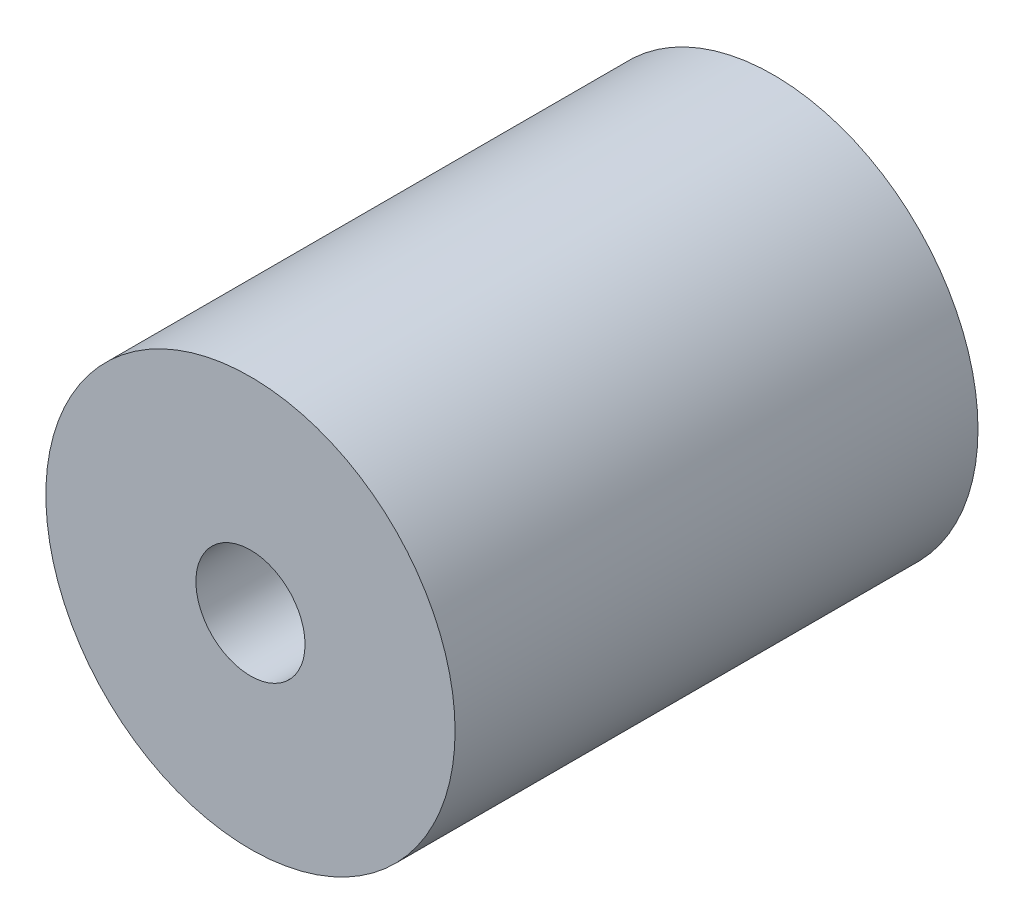
SolidWorks part; units mm, degrees
ref_plane "前视基准面" through (0, 0, 0) normal (0, 0, 1) x (1, 0, 0)
ref_plane "上视基准面" through (0, 0, 0) normal (0, 1, 0) x (1, 0, 0)
ref_plane "右视基准面" through (0, 0, 0) normal (1, 0, 0) x (0, 0, -1)
other "Configuration Table"
sketch "草图1" plane through (0, 0, 0) normal (0, 0, 1) x (1, 0, 0)
  line L0 (0, 0) -> (1.7387, 0.4659) construction
  line L1 (0, 0) -> (1.6291, 0.4551)
  line L2 (0, 0) -> (1.6291, -0.4551)
  line L3 (0, 0) -> (1.7387, -0.4659) construction
  line L4 (0, 0) -> (2.425, 0) construction
  line L5 (1.7387, 0.4659) -> (1.7387, -0.4659) construction
  circle A0 centre (0, 0) radius 1.525
  circle A1 centre (0, 0) radius 2.425
  circle A2 centre (0, 0) radius 1.6914 construction
  circle A3 centre (0, 0) radius 1.8 construction
  circle A4 centre (0, 0) radius 4.5
  spline S0 degree 4 poles (1.6291, 0.4551) (1.6415, 0.4586) (1.6769, 0.4656) (1.746, 0.4684) (1.8576, 0.4574) (1.9985, 0.4209) (2.171, 0.3489) (2.3582, 0.2351) (2.5438, 0.0819) (2.7191, -0.1093) (2.8693, -0.3205) (2.9946, -0.5472) (3.1006, -0.7975) (3.1986, -1.1195) (3.2658, -1.5159) (3.2754, -1.9832) (3.2064, -2.4974) (3.0631, -2.9965) (2.8558, -3.471) (2.5865, -3.9159) (2.2706, -4.3232) (1.901, -4.6937) (1.507, -5.0164) (1.0559, -5.3028) (0.6986, -5.4883) (0.2793, -5.6591) (0.0342, -5.7399) (-0.2484, -5.8241) (-0.3932, -5.8525) (-0.5197, -5.8826) (-0.5587, -5.8884) (-0.5863, -5.894) (-0.6011, -5.8971) knots 0 0 0 0 0 0.005604 0.015718 0.02996 0.048734 0.068727 0.096889 0.125051 0.153212 0.181374 0.209535 0.237696 0.271429 0.327752 0.384075 0.440398 0.496721 0.553044 0.609367 0.66569 0.722013 0.778336 0.834659 0.890982 0.909091 0.954545 0.977273 0.988636 0.994318 1 1 1 1 1 construction
  spline S1 degree 4 poles (1.6291, 0.4551) (1.6415, 0.4586) (1.6769, 0.4656) (1.746, 0.4684) (1.8576, 0.4574) (1.9985, 0.4209) (2.171, 0.3489) (2.3582, 0.2351) (2.5438, 0.0819) (2.7191, -0.1093) (2.8693, -0.3205) (2.9946, -0.5472) (3.1006, -0.7975) (3.1986, -1.1195) (3.2658, -1.5159) (3.2754, -1.9832) (3.2064, -2.4974) (3.0631, -2.9965) (2.8558, -3.471) (2.5865, -3.9159) (2.2706, -4.3232) (1.901, -4.6937) (1.507, -5.0164) (1.0559, -5.3028) (0.6986, -5.4883) (0.3874, -5.615) (0.2408, -5.6686) (0.2052, -5.6811) knots 0 0 0 0 0 0.005604 0.015718 0.02996 0.048734 0.068727 0.096889 0.125051 0.153212 0.181374 0.209535 0.237696 0.271429 0.327752 0.384075 0.440398 0.496721 0.553044 0.609367 0.66569 0.722013 0.778336 0.834659 0.890982 0.909091 0.909091 0.909091 0.909091 0.909091
  spline S2 degree 4 poles (1.6291, -0.4551) (1.6415, -0.4586) (1.6769, -0.4656) (1.746, -0.4684) (1.8576, -0.4574) (1.9985, -0.4209) (2.171, -0.3489) (2.3582, -0.2351) (2.5438, -0.0819) (2.7191, 0.1093) (2.8693, 0.3205) (2.9946, 0.5472) (3.1006, 0.7975) (3.1986, 1.1195) (3.2658, 1.5159) (3.2754, 1.9832) (3.2064, 2.4974) (3.0631, 2.9965) (2.8558, 3.471) (2.5865, 3.9159) (2.2706, 4.3232) (1.901, 4.6937) (1.507, 5.0164) (1.0559, 5.3028) (0.6986, 5.4883) (0.2793, 5.6591) (0.0342, 5.7399) (-0.2484, 5.8241) (-0.3932, 5.8525) (-0.5197, 5.8826) (-0.5587, 5.8884) (-0.5863, 5.894) (-0.6011, 5.8971) knots 0 0 0 0 0 0.005604 0.015718 0.02996 0.048734 0.068727 0.096889 0.125051 0.153212 0.181374 0.209535 0.237696 0.271429 0.327752 0.384075 0.440398 0.496721 0.553044 0.609367 0.66569 0.722013 0.778336 0.834659 0.890982 0.909091 0.954545 0.977273 0.988636 0.994318 1 1 1 1 1 construction
  spline S3 degree 4 poles (1.6291, -0.4551) (1.6415, -0.4586) (1.6769, -0.4656) (1.746, -0.4684) (1.8576, -0.4574) (1.9985, -0.4209) (2.171, -0.3489) (2.3582, -0.2351) (2.5438, -0.0819) (2.7191, 0.1093) (2.8693, 0.3205) (2.9946, 0.5472) (3.1006, 0.7975) (3.1986, 1.1195) (3.2658, 1.5159) (3.2754, 1.9832) (3.2064, 2.4974) (3.0631, 2.9965) (2.8558, 3.471) (2.5865, 3.9159) (2.2706, 4.3232) (1.901, 4.6937) (1.507, 5.0164) (1.0559, 5.3028) (0.6986, 5.4883) (0.3874, 5.615) (0.2408, 5.6686) (0.2052, 5.6811) knots 0 0 0 0 0 0.005604 0.015718 0.02996 0.048734 0.068727 0.096889 0.125051 0.153212 0.181374 0.209535 0.237696 0.271429 0.327752 0.384075 0.440398 0.496721 0.553044 0.609367 0.66569 0.722013 0.778336 0.834659 0.890982 0.909091 0.909091 0.909091 0.909091 0.909091
  point P16 (1.7387, 0)
  dimension "内啮合齿顶圆直径" = 3.05
  dimension "内啮合分度圆直径" = 3.6
  dimension "内啮合基圆直径" = 3.3829
  dimension "内啮合齿根圆直径" = 4.85
  dimension "外径" = 9
  dimension "渐开线镜像线夹角" = 15
extrude "凸台-拉伸1" add sketch "草图1" along normal blind 4 contours A4 | A0
extrude "切除-拉伸2" cut sketch "草图1<3>" along normal through all contours A0 S3 A1 S1 region at (1.9135, 0, 0)
sketch "草图1<3>" plane through (0, 0, 0) normal (0, 0, 1) x (1, 0, 0) same geometry as "草图1"
pattern_circular "阵列(圆周)1" count 9 over 360 about axis through (0, 0, 4) along (0, 0, 1) of "切除-拉伸2"
sketch "草图3" plane through (0, 0, 4) normal (0, 0, 1) x (1, 0, 0)
  circle A0 centre (0, 0) radius 4.5
  circle A1 centre (0, 0) radius 1.2
  circle A2 centre (0, 0) radius 4.5 construction
  dimension "D1" = 2.4
extrude "凸台-拉伸2" add sketch "草图3" along normal blind 1 contours A0
extrude "凸台-拉伸3" add sketch "草图3<3>" along normal blind 7.5 contours A0 | A1
sketch "草图3<3>" plane through (0, 0, 4) normal (0, 0, 1) x (1, 0, 0) same geometry as "草图3"
equation "\"m\"= 0.4'模数"
equation "\"z1\"= 6'外啮合齿轮数"
equation "\"a\"= 20度'压力角"
equation "\"z2\"= 9'内啮合齿轮数"
equation "\"hax\"= 1'齿顶高系数"
equation "\"cx\"= 0.25'顶隙系数"
equation "\"ha\"= \"hax\" * \"m\"'齿顶高"
equation "\"hf\"= ( \"hax\" + \"cx\" ) * \"m\"'齿根高"
equation "\"d1\"= \"m\" * \"z1\"'外啮合分度圆直径"
equation "\"da1\"= ( \"z1\" + 2 ) * \"m\"'外啮合齿顶圆直径"
equation "\"df1\"= \"d1\" - 2 * \"hf\"'外啮合齿根圆直径"
equation "\"db1\"= \"d1\" * cos ( \"a\" )'外啮合基圆直径"
equation "\"p\"= \"m\" * PI'齿距"
equation "\"d2\"= \"m\" * \"z2\"'内啮合分度圆直径"
equation "\"db2\"= \"d2\" * cos ( \"a\" )'内啮合基圆直径"
equation "\"da2\"= ( \"z2\" - 2 ) * \"m\"'内啮合齿顶圆直径"
equation "\"df2\"= \"d2\" + 2 * \"hf\"'内啮合齿根圆直径"
equation "\"内啮合齿顶圆直径@草图1\" = \"da2\" + 0.5 * \"hf\""
equation "\"内啮合齿根圆直径@草图1\"= \"df2\" + 0.5 * \"hf\""
equation "\"内啮合分度圆直径@草图1\"= \"d2\""
equation "\"内啮合基圆直径@草图1\"= \"db2\""
equation "\"渐开线镜像线夹角@草图1\"= 360度 / 4 / \"z2\" + 360度 / 4 / \"z2\" / 2"
equation "\"do\"= IIF ( \"edo\" >= ( \"df2\" + 1 ) , \"edo\" , ( \"df2\" + 1 ) )'外圈直径"
equation "\"h\"= 4'厚度"
equation "\"外径@草图1\"= \"do\""
equation "\"厚度@凸台-拉伸1\"= \"h\""
equation "\"内啮合齿轮数@阵列(圆周)1\"= \"z2\""
equation "\"edo\"= 9'期望的外圈直径"
